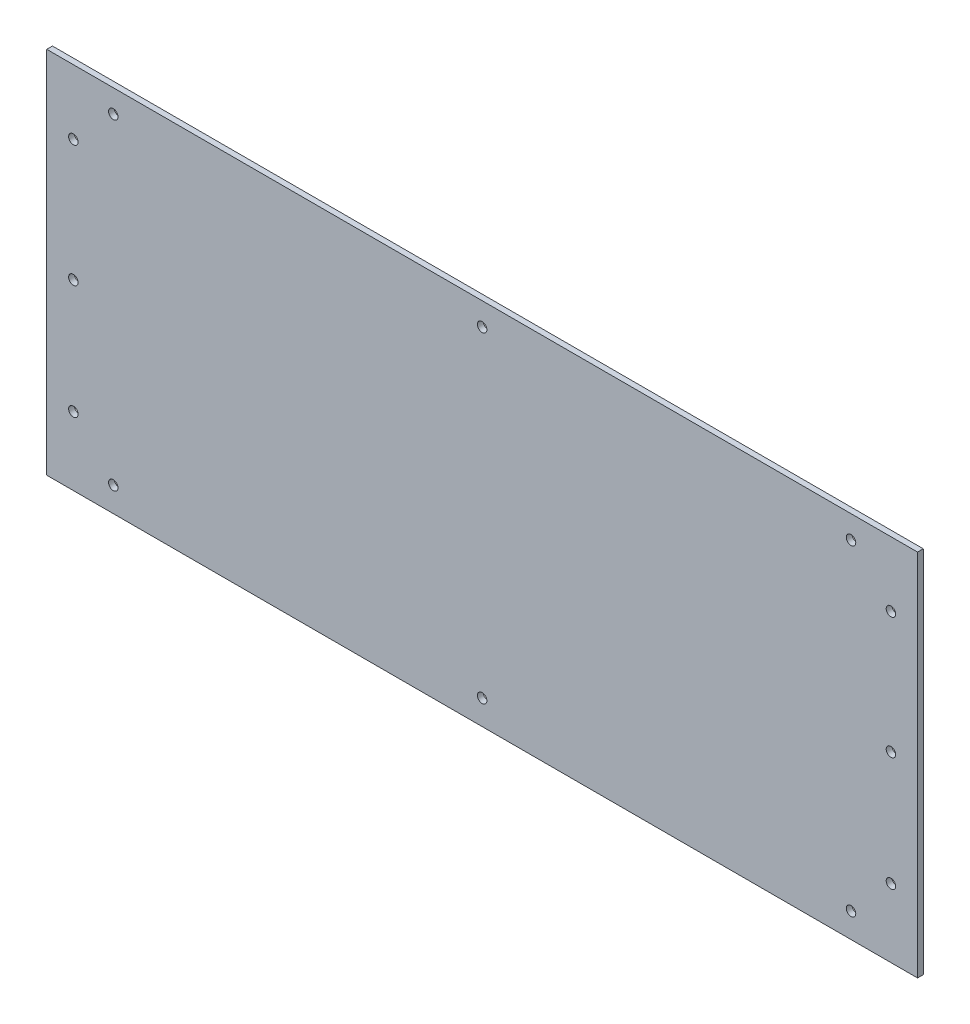
SolidWorks part; units mm, degrees
material "1345 Alloy"
ref_plane "Front Plane" through (0, 0, 0) normal (0, 0, 1) x (1, 0, 0)
ref_plane "Top Plane" through (0, 0, 0) normal (0, 1, 0) x (1, 0, 0)
ref_plane "Right Plane" through (0, 0, 0) normal (1, 0, 0) x (0, 0, -1)
sketch "Sketch1" plane through (0, 0, 0) normal (0, 0, 1) x (1, 0, 0)
  line L1 (-229, 96) -> (229, 96)
  line L2 (-229, 96) -> (-229, -96)
  line L3 (-229, -96) -> (229, -96)
  line L4 (229, 96) -> (229, -96)
  line L5 (-229, 96) -> (229, -96) construction
  line L6 (-229, -96) -> (229, 96) construction
  point P0 (0, 0)
  dimension "D1" = 458
  dimension "D2" = 192
extrude "Boss-Extrude1" add sketch "Sketch1" along normal blind 3
sketch "Sketch2" plane through (0, 0, 3) normal (0, 0, 1) x (1, 0, 0)
  line L0 (-229, 96) -> (-229, 86) construction
  line L1 (-229, 96) -> (-194, 96) construction
  line L2 (-194, 96) -> (-194, 86) construction
  line L3 (-194, 86) -> (-229, 86) construction
  line L4 (-194, -83.0046) -> (194, -83.0046) construction
  line L6 (0, -83) -> (0, -96) construction
  line L7 (194, -96.0046) -> (194, -83.0046) construction
  line L8 (194, 86) -> (194, 96) construction
  line L9 (-229, 0) -> (-215, 0) construction
  line L10 (-215, 0) -> (-215, 64) construction
  line L11 (-215, 0) -> (-215, -60) construction
  line L12 (229, 0) -> (215, 0) construction
  line L13 (0, 86) -> (-194, 86) construction
  line L14 (215, 64) -> (215, 96) construction
  line L15 (215, 0) -> (215, 64) construction
  line L16 (215, 0) -> (215, -60) construction
  line L17 (0, 86) -> (194, 86) construction
  line L18 (229, 96) -> (-229, 96) construction
  line L19 (-229, -96) -> (229, -96) construction
  line L22 (-215, 64) -> (-215, 96) construction
  circle A0 centre (-194, 86) radius 2.5
  circle A1 centre (-194, -83.0046) radius 2.5
  circle A2 centre (194, -83.0046) radius 2.5
  circle A3 centre (194, 86) radius 2.5
  circle A4 centre (-215, 0) radius 2.5
  circle A5 centre (-215, -60) radius 2.5
  circle A6 centre (-215, 64) radius 2.5
  circle A7 centre (215, 0) radius 2.5
  circle A8 centre (215, -60) radius 2.5
  circle A9 centre (215, 64) radius 2.5
  circle A10 centre (0, 86) radius 2.5
  circle A11 centre (0, -83) radius 2.5
  dimension "D3" = 5
  dimension "D6" = 5
  dimension "D7" = 5
  dimension "D8" = 5
  dimension "D13" = 5
  dimension "D14" = 5
  dimension "D15" = 5
  dimension "D19" = 5
  dimension "D20" = 5
  dimension "D1" = 10
  dimension "D2" = 35
  dimension "D4" = 13
  dimension "D5" = 12.9954
  dimension "D9" = 13
  dimension "D10" = 14
  dimension "D11" = 64
  dimension "D12" = 60
  dimension "D16" = 14
  dimension "D17" = 64
  dimension "D18" = 60
  dimension "D22" = 194
  dimension "D23" = 194
  dimension "D24" = 32
  dimension "D25" = 32
extrude "Cut-Extrude1" cut sketch "Sketch2" against normal through all
sketch "Sketch3" plane through (0, 0, 3) normal (0, 0, 1) x (1, 0, 0)
  line L1 (-229, 96) -> (229, 96)
  line L2 (-229, 96) -> (-229, 98)
  line L3 (-229, 98) -> (229, 98)
  line L4 (229, 96) -> (229, 98)
  dimension "D1" = 458
  dimension "D2" = 2
extrude "Boss-Extrude2" add sketch "Sketch3" against normal through all
